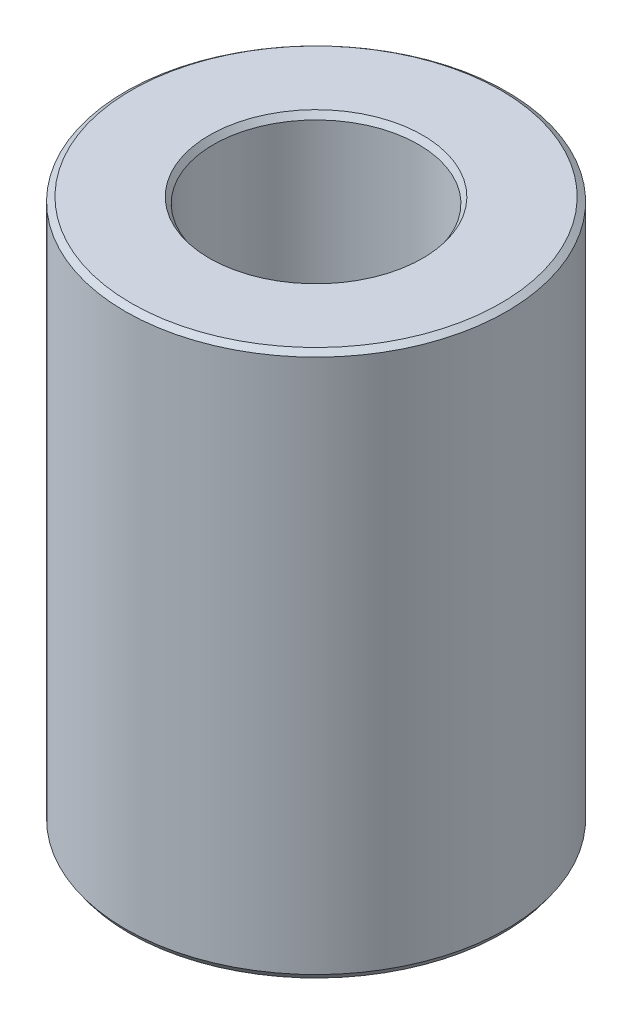
SolidWorks part; units mm, degrees
ref_plane "Front Plane" through (0, 0, 0) normal (0, 0, 1) x (1, 0, 0)
ref_plane "Top Plane" through (0, 0, 0) normal (0, 1, 0) x (1, 0, 0)
ref_plane "Right Plane" through (0, 0, 0) normal (1, 0, 0) x (0, 0, -1)
sketch "Sketch1" plane through (0, 0, 0) normal (0, 1, 0) x (1, 0, 0)
  circle A0 centre (0, 0) radius 25
  dimension "SLEEVE_OD" = 50
extrude "Boss-Extrude1" add sketch "Sketch1" along normal blind 71.4663
sketch "Sketch2" plane through (0, 0, 0) normal (0, 1, 0) x (1, 0, 0)
  circle A0 centre (0, 0) radius 13.4402
  dimension "BORE_D" = 26.8803
extrude "Cut-Extrude1" cut sketch "Sketch2" along normal through all
chamfer "Chamfer1" distance 0.5505 angle 54.771 4 edges at (0, 71.4663, 13.4402) (0, 0, 13.4402) (0, 0, 25) (0, 71.4663, 25) first distance on face at (0, 71.4663, 13.4402) first distance on face at (0, 0, 13.4402) first distance on face at (0, 71.4663, 25)
